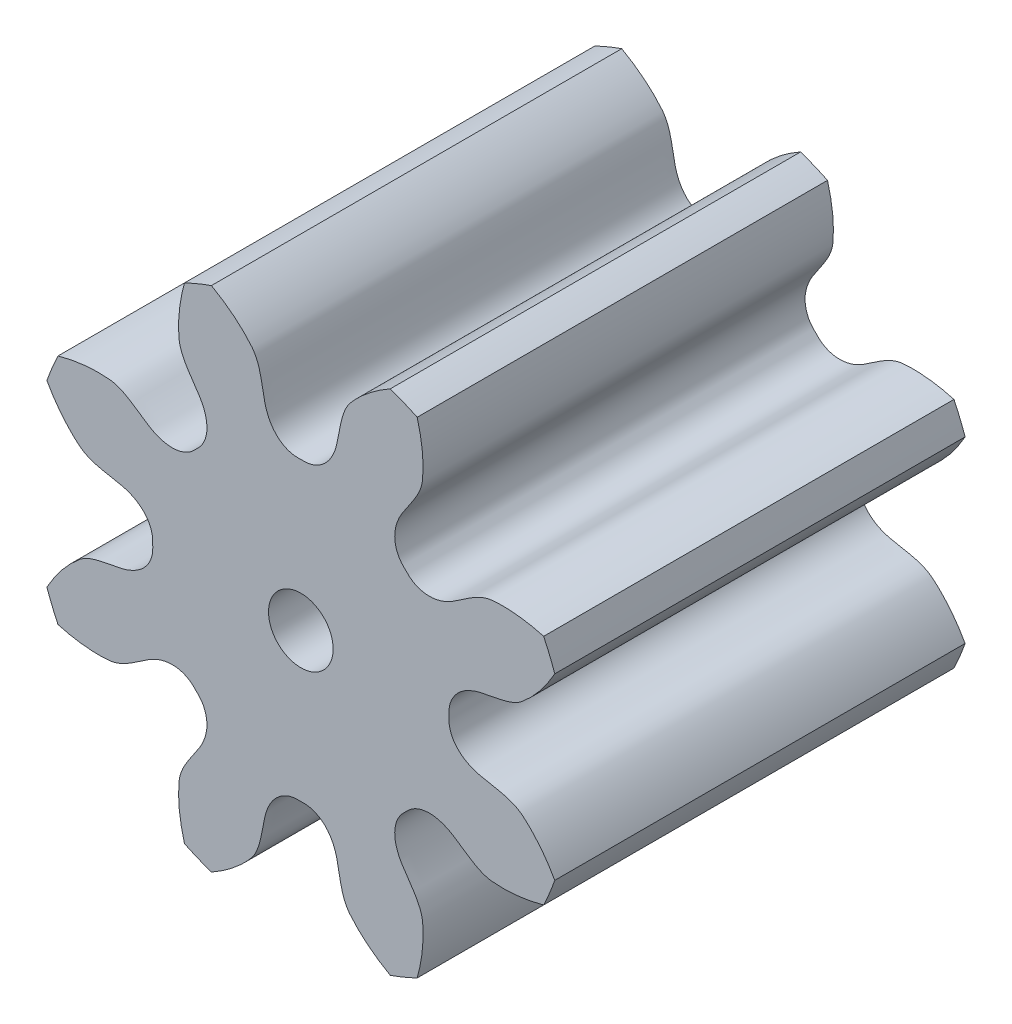
SolidWorks part; units mm, degrees
material "高韧性光敏树脂"
ref_plane "前视基准面" through (0, 0, 0) normal (0, 0, 1) x (1, 0, 0)
ref_plane "上视基准面" through (0, 0, 0) normal (0, 1, 0) x (1, 0, 0)
ref_plane "右视基准面" through (0, 0, 0) normal (1, 0, 0) x (0, 0, -1)
ref_axis "基准轴1" through (0, 0, 55) along (0, 0, -1)
sketch "SketchRevolveSpurGear1" plane through (0, 0, 0) normal (1, 0, 0) x (0, 0, -1)
  line L0 (0, 0) -> (1, 0) construction
  line L1 (-9.525, 0) -> (-9.525, 12.5)
  line L2 (-9.525, 12.5) -> (9.525, 12.5)
  line L3 (9.525, 12.5) -> (9.525, 0)
  line L4 (9.525, 0) -> (-9.525, 0)
revolve "SpurGear1" add sketch "SketchRevolveSpurGear1" angle 360 about L0
sketch "SketchToothSpurGear1" plane through (0, 0, 0) normal (0, 0, 1) x (1, 0, 0)
  arc A0 (11.8708, 4.2983) -> (11.8708, -4.2983) centre (0, 0) cw
  spline S0 degree 3 poles (11.8708, -4.2983) (11.7054, -3.9899) (11.4661, -3.6029) (11.1329, -3.1632) (10.9456, -2.9376) (10.7609, -2.7348) (10.581, -2.5534) (10.4063, -2.3946) (9.7527, -1.8246) (8.8695, -1.8284) (8.1725, -1.6298) (8.1519, -1.6237) (8.1313, -1.6175) (8.1108, -1.6111) (8.0904, -1.6045) (8.0701, -1.5977) (8.0499, -1.5908) (8.0297, -1.5837) (8.0096, -1.5764) (7.9897, -1.569) (7.9698, -1.5614) (7.95, -1.5536) (7.9302, -1.5456) (7.9106, -1.5375) (7.891, -1.5291) (7.8716, -1.5206) (7.8522, -1.5119) (7.8329, -1.503) (7.8137, -1.4939) (7.7946, -1.4847) (7.7756, -1.4752) (7.7567, -1.4655) (7.7378, -1.4557) (7.7191, -1.4456) (7.7005, -1.4354) (7.6819, -1.4249) (7.6635, -1.4142) (7.6451, -1.4033) (7.6269, -1.3922) (7.6087, -1.3809) (7.5907, -1.3694) (7.5728, -1.3577) (7.5549, -1.3457) (7.5372, -1.3335) (7.5196, -1.3211) (7.5021, -1.3084) (7.4848, -1.2955) (7.4675, -1.2824) (7.4504, -1.269) (7.4334, -1.2554) (7.4165, -1.2416) (7.3998, -1.2275) (7.3832, -1.2131) (7.3667, -1.1985) (7.3504, -1.1836) (7.3342, -1.1685) (7.3182, -1.1531) (7.3024, -1.1375) (7.2867, -1.1215) (7.2711, -1.1053) (7.2558, -1.0889) (7.2406, -1.0721) (7.2257, -1.0551) (7.2109, -1.0378) (7.1963, -1.0202) (7.1819, -1.0023) (7.1677, -0.9841) (7.1538, -0.9657) (7.1401, -0.947) (7.1266, -0.9279) (7.1134, -0.9086) (7.1004, -0.889) (7.0877, -0.8691) (7.0752, -0.849) (7.063, -0.8285) (7.0511, -0.8078) (7.0396, -0.7867) (7.0283, -0.7654) (7.0173, -0.7438) (7.0067, -0.722) (6.9964, -0.6999) (6.9865, -0.6775) (6.9769, -0.6548) (6.9677, -0.6319) (6.9588, -0.6088) (6.9503, -0.5854) (6.9423, -0.5618) (6.9346, -0.5379) (6.9274, -0.5138) (6.9206, -0.4896) (6.9142, -0.4651) (6.9083, -0.4405) (6.9028, -0.4156) (6.8977, -0.3907) (6.8932, -0.3655) (6.8891, -0.3403) (6.8854, -0.3149) (6.8823, -0.2894) (6.8796, -0.2638) (6.8775, -0.2381) (6.8758, -0.2123) (6.8746, -0.1865) (6.874, -0.1607) (6.8738, -0.1374) (6.8743, -0.0838) (6.8756, 0) (6.8743, 0.0838) (6.8738, 0.1374) (6.874, 0.1607) (6.8746, 0.1865) (6.8758, 0.2123) (6.8775, 0.2381) (6.8796, 0.2638) (6.8823, 0.2894) (6.8854, 0.3149) (6.8891, 0.3403) (6.8932, 0.3655) (6.8977, 0.3907) (6.9028, 0.4156) (6.9083, 0.4405) (6.9142, 0.4651) (6.9206, 0.4896) (6.9274, 0.5138) (6.9346, 0.5379) (6.9423, 0.5618) (6.9503, 0.5854) (6.9588, 0.6088) (6.9677, 0.6319) (6.9769, 0.6548) (6.9865, 0.6775) (6.9964, 0.6999) (7.0067, 0.722) (7.0173, 0.7438) (7.0283, 0.7654) (7.0396, 0.7867) (7.0511, 0.8078) (7.063, 0.8285) (7.0752, 0.849) (7.0877, 0.8691) (7.1004, 0.889) (7.1134, 0.9086) (7.1266, 0.9279) (7.1401, 0.947) (7.1538, 0.9657) (7.1677, 0.9841) (7.1819, 1.0023) (7.1963, 1.0202) (7.2109, 1.0378) (7.2257, 1.0551) (7.2406, 1.0721) (7.2558, 1.0889) (7.2711, 1.1053) (7.2867, 1.1215) (7.3024, 1.1375) (7.3182, 1.1531) (7.3342, 1.1685) (7.3504, 1.1836) (7.3667, 1.1985) (7.3832, 1.2131) (7.3998, 1.2275) (7.4165, 1.2416) (7.4334, 1.2554) (7.4504, 1.269) (7.4675, 1.2824) (7.4848, 1.2955) (7.5021, 1.3084) (7.5196, 1.3211) (7.5372, 1.3335) (7.5549, 1.3457) (7.5728, 1.3577) (7.5907, 1.3694) (7.6087, 1.3809) (7.6269, 1.3922) (7.6451, 1.4033) (7.6635, 1.4142) (7.6819, 1.4249) (7.7005, 1.4354) (7.7191, 1.4456) (7.7378, 1.4557) (7.7567, 1.4655) (7.7756, 1.4752) (7.7946, 1.4847) (7.8137, 1.4939) (7.8329, 1.503) (7.8522, 1.5119) (7.8716, 1.5206) (7.891, 1.5291) (7.9106, 1.5375) (7.9302, 1.5456) (7.95, 1.5536) (7.9698, 1.5614) (7.9897, 1.569) (8.0096, 1.5764) (8.0297, 1.5837) (8.0499, 1.5908) (8.0701, 1.5977) (8.0904, 1.6045) (8.1108, 1.6111) (8.1313, 1.6175) (8.1519, 1.6237) (8.1725, 1.6298) (8.8695, 1.8284) (9.7527, 1.8246) (10.4063, 2.3946) (10.581, 2.5534) (10.7609, 2.7348) (10.9456, 2.9376) (11.1329, 3.1632) (11.4661, 3.6029) (11.7054, 3.9899) (11.8708, 4.2983) knots 0 0 0 0 0.074363 0.096474 0.117246 0.136677 0.154768 0.17152 0.186931 0.337992 0.33952 0.341045 0.342568 0.344089 0.345608 0.347125 0.34864 0.350154 0.351666 0.353177 0.354686 0.356194 0.357702 0.359209 0.360715 0.36222 0.363725 0.36523 0.366735 0.36824 0.369745 0.37125 0.372757 0.374264 0.375771 0.37728 0.37879 0.380302 0.381815 0.38333 0.384847 0.386366 0.387888 0.389412 0.390939 0.392468 0.394001 0.395537 0.397077 0.39862 0.400167 0.401717 0.403273 0.404832 0.406396 0.407965 0.409539 0.411118 0.412702 0.414292 0.415887 0.417488 0.419095 0.420708 0.422328 0.423953 0.425585 0.427224 0.428869 0.430521 0.43218 0.433846 0.435519 0.437199 0.438886 0.44058 0.442281 0.443989 0.445704 0.447427 0.449156 0.450892 0.452635 0.454385 0.456141 0.457903 0.459672 0.461447 0.463227 0.465013 0.466805 0.468601 0.470403 0.472209 0.474019 0.475833 0.477651 0.479471 0.481295 0.483121 0.48495 0.48678 0.488611 0.490443 0.491735 0.5 0.508265 0.509557 0.511389 0.51322 0.51505 0.516879 0.518705 0.520529 0.522349 0.524167 0.525981 0.527791 0.529597 0.531399 0.533195 0.534987 0.536773 0.538553 0.540328 0.542097 0.543859 0.545615 0.547365 0.549108 0.550844 0.552573 0.554296 0.556011 0.557719 0.55942 0.561114 0.562801 0.564481 0.566154 0.56782 0.569479 0.571131 0.572776 0.574415 0.576047 0.577672 0.579292 0.580905 0.582512 0.584113 0.585708 0.587298 0.588882 0.590461 0.592035 0.593604 0.595168 0.596727 0.598283 0.599833 0.60138 0.602923 0.604463 0.605999 0.607532 0.609061 0.610588 0.612112 0.613634 0.615153 0.61667 0.618185 0.619698 0.62121 0.62272 0.624229 0.625736 0.627243 0.62875 0.630255 0.63176 0.633265 0.63477 0.636275 0.63778 0.639285 0.640791 0.642298 0.643806 0.645314 0.646823 0.648334 0.649846 0.65136 0.652875 0.654392 0.655911 0.657432 0.658955 0.66048 0.662008 0.813069 0.82848 0.845232 0.863323 0.882754 0.903526 0.925637 1 1 1 1
extrude "ToothExtrudeCutSpurGear1" cut sketch "SketchToothSpurGear1" against normal blind 9.525 and the other way blind 9.525
pattern_circular "PatternSpurGear1" count 8 every 45 about axis through (0, 0, 55) along (0, 0, -1) of "ToothExtrudeCutSpurGear1"
sketch "BoreRevolveSketch" plane through (0, 0, 0) normal (1, 0, 0) x (0, 0, -1)
  line L0 (0, 0) -> (1, 0) construction
  line L1 (-9.525, 0) -> (9.525, 0)
  line L2 (9.525, 0) -> (9.525, 1.5)
  line L3 (9.525, 1.5) -> (-9.525, 1.5)
  line L4 (-9.525, 1.5) -> (-9.525, 0)
  dimension "TaperSide1" = 1.5
  dimension "TaperSide2" = 1.5
revolve "BoreRevolveCut" cut sketch "BoreRevolveSketch" angle 360 about L0
sketch "AuxiliarySketchSpurGear1" plane through (0, 0, 0) normal (0, 0, 1) x (1, 0, 0)
  circle A0 centre (0, 0) radius 10 construction
  circle A1 centre (0, 0) radius 9.3969 construction
  circle A2 centre (0, 0) radius 10.1791 construction
  circle A3 centre (0, 0) radius 12.5 construction
  circle A4 centre (0, 0) radius 6.875 construction
  dimension "PitchDiameter" = 20
  dimension "BaseDiameter" = 18.7939
  dimension "FormDiameter" = 20.3583
  dimension "MajorDiameter" = 25
  dimension "MinorDiameter" = 13.75
scale "缩放比例1" scale about origin uniform scaling yes scale factor 0.2
